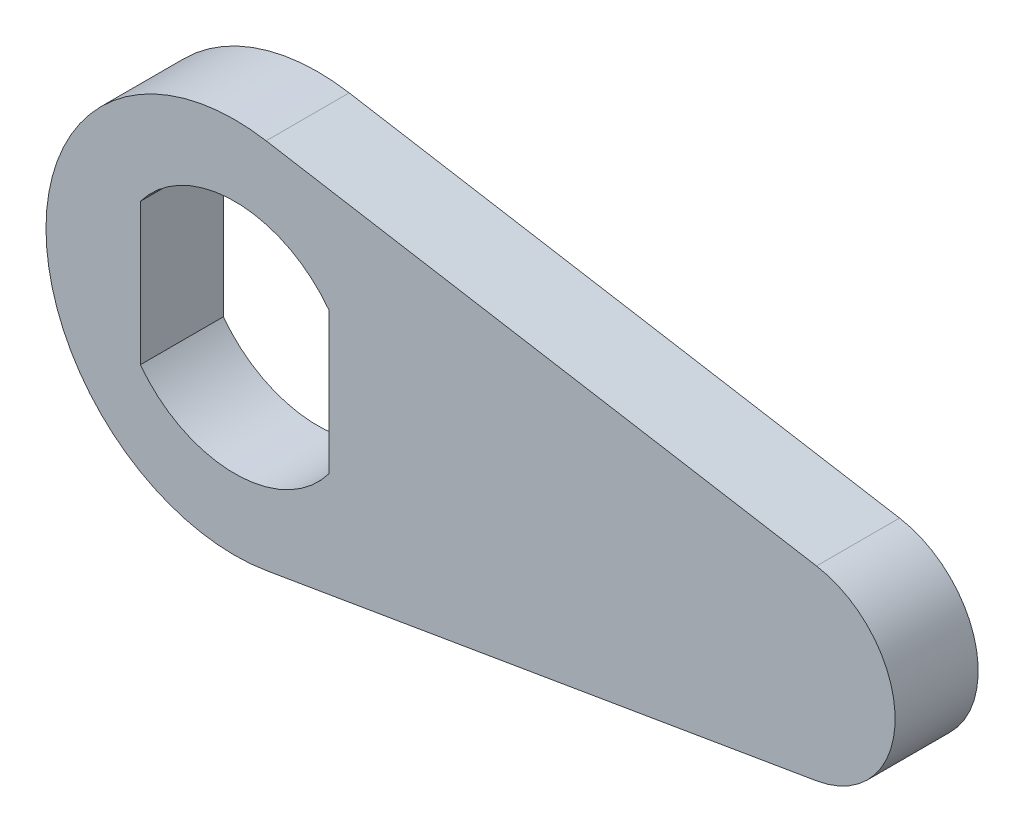
SolidWorks part; units mm, degrees
ref_plane "XY" through (0, 0, 0) normal (0, 0, 1) x (1, 0, 0)
ref_plane "XZ" through (0, 0, 0) normal (0, 1, 0) x (1, 0, 0)
ref_plane "YZ" through (0, 0, 0) normal (1, 0, 0) x (0, 0, -1)
ref_axis "X" through (-8.0962, 0, 0) along (1, 0, 0)
ref_axis "Y" through (0, -6.985, 0) along (0, 1, 0)
ref_axis "Z" through (0, 0, 2.9337) along (0, 0, -1)
sketch "Sketch1" plane through (0, 0, 0) normal (0, 0, 1) x (1, 0, 0)
  line L0 (1.0583, 6.2612) -> (19.5792, 3.1306)
  line L1 (19.5792, -3.1306) -> (1.0583, -6.2612)
  line L2 (0, 0) -> (19.05, 0) construction
  line L3 (1.0583, 6.2612) -> (1.0583, -6.2612) construction
  line L6 (-3.175, 2.3812) -> (-3.175, -2.3812)
  line L7 (3.175, 2.3812) -> (3.175, -2.3812)
  arc A0 (1.0583, 6.2612) -> (1.0583, -6.2612) centre (0, 0) ccw
  arc A1 (-3.175, -2.3812) -> (3.175, -2.3812) centre (0, 0) ccw
  arc A2 (19.5792, 3.1306) -> (19.5792, -3.1306) centre (19.05, 0) cw
  arc A3 (3.175, 2.3812) -> (-3.175, 2.3812) centre (0, 0) ccw
  dimension "D1" = 7.9375
  dimension "D2" = 6.35
  dimension "D5" = 3.175
  dimension "D3" = 6.35
  dimension "D4" = 19.05
extrude "Boss-Extrude1" add sketch "Sketch1" along normal blind 2.794
ref_axis "Axis1" through (19.05, 0, 2.794) along (0, 0, -1)
